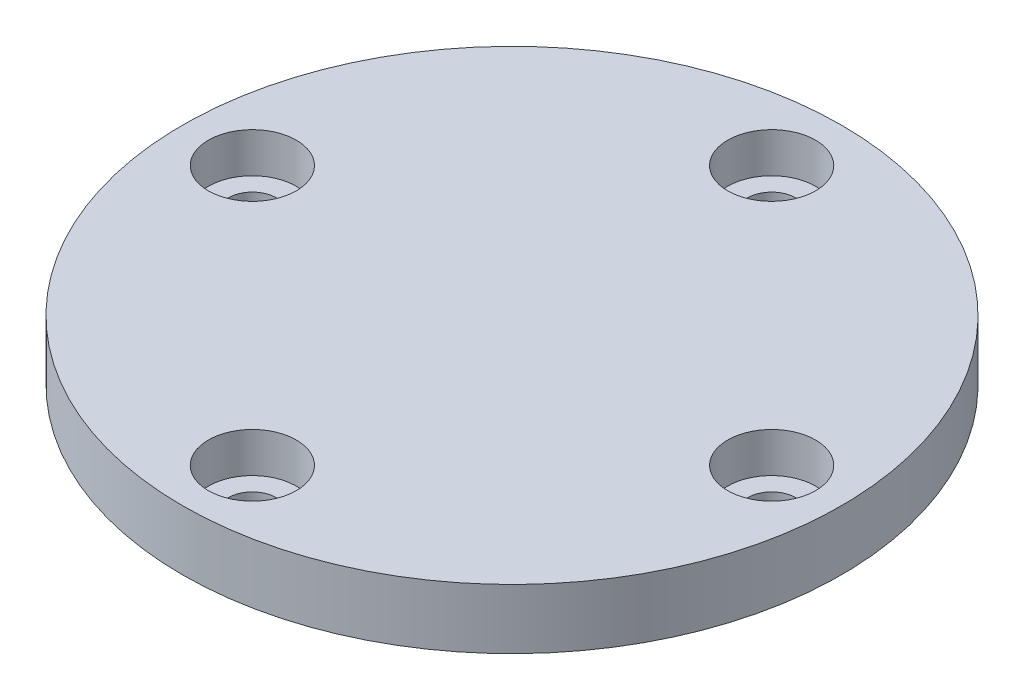
SolidWorks part; units mm, degrees
material "1060 Alloy"
ref_plane "Front Plane" through (0, 0, 0) normal (0, 0, 1) x (1, 0, 0)
ref_plane "Top Plane" through (0, 0, 0) normal (0, 1, 0) x (1, 0, 0)
ref_plane "Right Plane" through (0, 0, 0) normal (1, 0, 0) x (0, 0, -1)
sketch "Sketch1" plane through (0, 0, 0) normal (0, 1, 0) x (1, 0, 0)
  circle A0 centre (0, 0) radius 16.5
  dimension "D1" = 33
extrude "Boss-Extrude1" add sketch "Sketch1" along normal blind 3
sketch "Sketch7" plane through (0, 3, 0) normal (0, 1, 0) x (1, 0, 0)
  circle A0 centre (0, -10.25) radius 0.25
  circle A1 centre (0, 0) radius 9.8
  dimension "D1" = 0.5
  dimension "D2" = 10.25
  dimension "D3" = 19.6
sketch "Sketch8" plane through (0, 3, 0) normal (0, 1, 0) x (1, 0, 0)
  line L0 (0, 0) -> (13.2071, 13.2071) construction
  circle A0 centre (7.7782, 7.7782) radius 1
  dimension "D1" = 2
  dimension "D2" = 11
sketch "Sketch9" plane through (0, 3, 0) normal (0, 1, 0) x (1, 0, 0)
  circle A0 centre (0, 0) radius 11
  dimension "D1" = 22
hole_wizard "CBORE for M2 SHCS1" positions "Sketch13" profile "Sketch14" counterbore size "M2" standard "ANSI Metric" end condition through all
sketch "Sketch13" plane through (0, 3, 0) normal (0, 1, 0) x (1, 0, 0)
  circle A0 centre (0, 0) radius 11 construction
  point P0 (-13, 0)
  dimension "D1" = 13
sketch "Sketch14" plane through (-13, 3, 0) normal (1, 0, 0) x (0, 0, 1)
  line L0 (0, 0) -> (0, 3)
  line L1 (0, 3) -> (1.2, 3)
  line L3 (1.2, 3) -> (1.2, 2)
  line L4 (1.2, 2) -> (2.2, 2)
  line L5 (2.2, 2) -> (2.2, 0)
  line L7 (2.2, 0) -> (0, 0)
  line L11 (0, -6.35) -> (0, 107.95) construction
  dimension "Thru Hole Dia." = 2.4
  dimension "Thru Hole Depth" = 3
  dimension "C'Bore Dia." = 4.4
  dimension "C'Bore Depth" = 2
pattern_circular "CirPattern1" count 4 over 360 about axis through (0, 3, 0) along (0, 1, 0) of "CBORE for M2 SHCS1"
